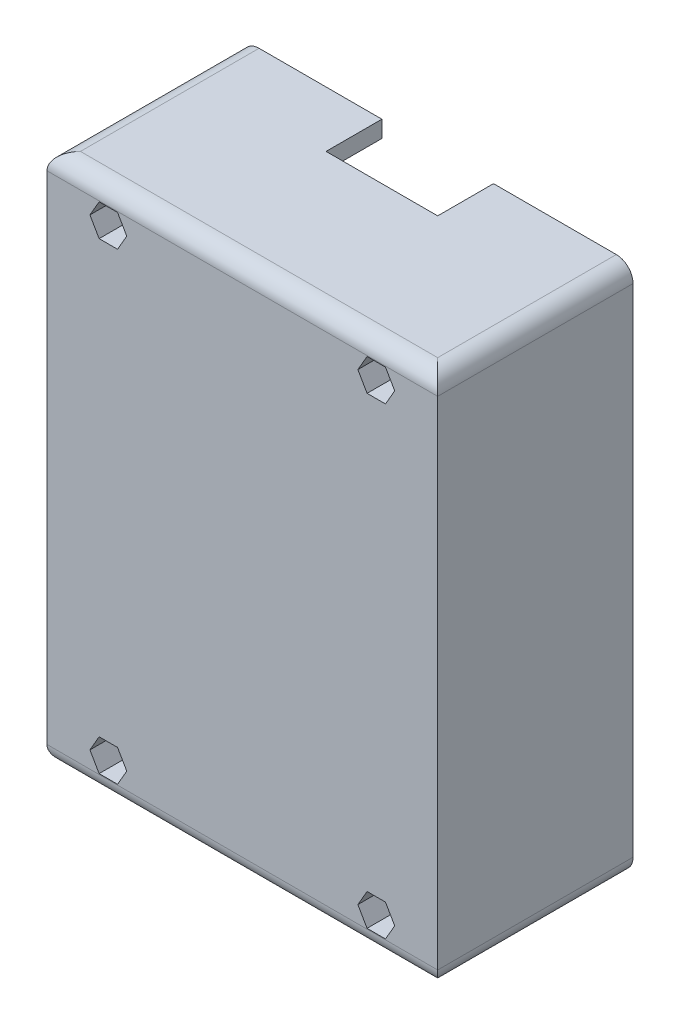
SolidWorks part; units mm, degrees
ref_plane "前视基准面" through (0, 0, 0) normal (0, 0, 1) x (1, 0, 0)
ref_plane "上视基准面" through (0, 0, 0) normal (0, 1, 0) x (1, 0, 0)
ref_plane "右视基准面" through (0, 0, 0) normal (1, 0, 0) x (0, 0, -1)
other "Configuration Table"
sketch "草图1" plane through (0, 0, 0) normal (1, 0, 0) x (0, 0, -1)
  line L1 (-17.5, -47.5) -> (17.5, -47.5)
  line L2 (-17.5, -47.5) -> (-17.5, 47.5)
  line L3 (-17.5, 47.5) -> (17.5, 47.5)
  line L4 (17.5, -47.5) -> (17.5, 47.5)
  line L5 (-17.5, -47.5) -> (17.5, 47.5) construction
  line L6 (-17.5, 47.5) -> (17.5, -47.5) construction
  point P0 (0, 0)
  dimension "D1" = 35
  dimension "D2" = 95
extrude "凸台-拉伸1" add sketch "草图1" along normal blind 60
sketch "草图4" plane through (0, 0, 17.5) normal (0, 0, 1) x (1, 0, 0)
  line L1 (50.7, 41.5) -> (52.35, 38.6421)
  line L2 (52.35, 38.6421) -> (55.65, 38.6421)
  line L3 (55.65, 38.6421) -> (57.3, 41.5)
  line L4 (57.3, 41.5) -> (55.65, 44.3579)
  line L5 (55.65, 44.3579) -> (52.35, 44.3579)
  line L6 (52.35, 44.3579) -> (50.7, 41.5)
  line L7 (9.3, 41.5) -> (7.65, 44.3579)
  line L8 (6, 41.5) -> (6, -41.5)
  line L9 (6, -41.5) -> (54, -41.5)
  line L10 (54, -41.5) -> (54, 41.5)
  line L11 (54, 41.5) -> (6, 41.5)
  line L12 (6, 41.5) -> (6, -41.5) construction
  line L13 (6, -41.5) -> (54, -41.5) construction
  line L14 (54, -41.5) -> (54, 41.5) construction
  line L15 (54, 41.5) -> (6, 41.5) construction
  line L16 (7.65, 44.3579) -> (4.35, 44.3579)
  line L17 (4.35, 44.3579) -> (2.7, 41.5)
  line L18 (2.7, 41.5) -> (4.35, 38.6421)
  line L19 (4.35, 38.6421) -> (7.65, 38.6421)
  line L20 (7.65, 38.6421) -> (9.3, 41.5)
  line L21 (9.3, -41.5) -> (7.65, -38.6421)
  line L22 (7.65, -38.6421) -> (4.35, -38.6421)
  line L23 (4.35, -38.6421) -> (2.7, -41.5)
  line L24 (2.7, -41.5) -> (4.35, -44.3579)
  line L25 (4.35, -44.3579) -> (7.65, -44.3579)
  line L26 (7.65, -44.3579) -> (9.3, -41.5)
  line L27 (50.7, -41.5) -> (52.35, -44.3579)
  line L28 (52.35, -44.3579) -> (55.65, -44.3579)
  line L29 (55.65, -44.3579) -> (57.3, -41.5)
  line L30 (57.3, -41.5) -> (55.65, -38.6421)
  line L31 (55.65, -38.6421) -> (52.35, -38.6421)
  line L32 (52.35, -38.6421) -> (50.7, -41.5)
  circle A0 centre (54, 41.5) radius 3.3 construction
  circle A1 centre (6, 41.5) radius 3.3 construction
  circle A2 centre (6, -41.5) radius 3.3 construction
  circle A3 centre (54, -41.5) radius 3.3 construction
  dimension "D2" = 6.6
  dimension "D3" = 6.6
  dimension "D4" = 6.6
  dimension "D5" = 6.6
  dimension "D1" = 6
extrude "切除-拉伸1" cut sketch "草图4" against normal blind 32
sketch "草图5" plane through (0, 0, 17.5) normal (0, 0, 1) x (1, 0, 0)
  circle A0 centre (54, 41.5) radius 1.6
  circle A1 centre (6, 41.5) radius 1.6
  circle A2 centre (54, -41.5) radius 1.6
  circle A3 centre (6, -41.5) radius 1.6
  dimension "D1" = 3.2
  dimension "D2" = 3.2
  dimension "D3" = 3.2
  dimension "D4" = 3.2
extrude "切除-拉伸2" cut sketch "草图5" against normal through all
sketch "草图6" plane through (0, 0, 0) normal (-1, 0, 0) x (0, 0, 1)
  line L4 (-17.5, 47.5) -> (-17.5, -47.5)
  line L5 (-17.5, -47.5) -> (17.5, -47.5)
  line L6 (17.5, -47.5) -> (17.5, 47.5)
  line L7 (17.5, 47.5) -> (-17.5, 47.5)
  line L8 (-17.5, 47.5) -> (-17.5, -47.5)
  line L9 (-17.5, -47.5) -> (17.5, -47.5)
  line L10 (17.5, -47.5) -> (17.5, 47.5)
  line L11 (17.5, 47.5) -> (-17.5, 47.5)
  dimension "D1" = 0
extrude "凸台-拉伸2" add sketch "草图6" along normal blind 5
sketch "草图7" plane through (60, 0, 0) normal (1, 0, 0) x (0, 0, -1)
  line L4 (17.5, -47.5) -> (17.5, 47.5)
  line L5 (17.5, 47.5) -> (-17.5, 47.5)
  line L6 (-17.5, 47.5) -> (-17.5, -47.5)
  line L7 (-17.5, -47.5) -> (17.5, -47.5)
  line L8 (17.5, -47.5) -> (17.5, 47.5)
  line L9 (17.5, 47.5) -> (-17.5, 47.5)
  line L10 (-17.5, 47.5) -> (-17.5, -47.5)
  line L11 (-17.5, -47.5) -> (17.5, -47.5)
  dimension "D1" = 0
extrude "凸台-拉伸3" add sketch "草图7" along normal blind 5
shell "抽壳1" thickness 3 removed face at (7.6, 41.5, -17.5)
ref_plane "基准面1" through (0, 0, -1.5) normal (0, 0, -1) x (-1, 0, 0)
sketch "草图8" plane through (0, 0, -1.5) normal (0, 0, -1) x (-1, 0, 0)
  line L0 (2, -44.5) -> (2, 44.5) construction
  line L5 (2, 29) -> (-6, 29)
  line L6 (-62, -44.5) -> (-62, 44.5) construction
  line L7 (-60, 34.5) -> (0, 34.5) construction
  line L8 (-60, 34.5) -> (-60, -15.5) construction
  line L9 (-60, -15.5) -> (0, -15.5) construction
  line L10 (0, 34.5) -> (0, -15.5) construction
  line L12 (-58, 32.5) -> (-58, -13.5) construction
  line L13 (-58, -13.5) -> (-2, -13.5) construction
  line L14 (-2, 32.5) -> (-2, -13.5) construction
  line L15 (-58, 32.5) -> (-2, 32.5) construction
  line L16 (-62, 36) -> (-54, 36)
  line L21 (2, 29) -> (2, 36)
  line L22 (2, 36) -> (-6, 36)
  line L23 (-6, 29) -> (-6, 36)
  line L24 (-2, 9.5) -> (-30, 9.5) construction
  line L25 (-30, 9.5) -> (-30, 18.3227) construction
  line L26 (-54, 29) -> (-54, 36)
  line L27 (-62, 29) -> (-54, 29)
  line L28 (-62, 29) -> (-62, 36)
  line L29 (2, -17) -> (-6, -17)
  line L30 (-6, -10) -> (-6, -17)
  line L31 (2, -10) -> (-6, -10)
  line L32 (2, -10) -> (2, -17)
  line L33 (-62, -10) -> (-62, -17)
  line L34 (-62, -10) -> (-54, -10)
  line L35 (-54, -10) -> (-54, -17)
  line L36 (-62, -17) -> (-54, -17)
  circle A0 centre (-2, 32.5) radius 1.5301
  circle A1 centre (-58, 32.5) radius 1.5301
  circle A2 centre (-2, -13.5) radius 1.5301
  circle A3 centre (-58, -13.5) radius 1.5301
  dimension "D1" = 60
  dimension "D2" = 50
  dimension "D3" = 2
  dimension "D6" = 7
  dimension "D7" = 3.5
  dimension "D8" = 8
  dimension "D5" = 2
extrude "凸台-拉伸4" add sketch "草图8" against normal blind 5
sketch "草图9" plane through (54, 0, 0) normal (-1, 0, 0) x (0, 0, 1)
  line L0 (0.3, 35.25) -> (0.3, 29.75)
  line L4 (2.8, 35.25) -> (2.8, 29.75)
  line L5 (-1.5, 36) -> (-1.5, 29) construction
  line L7 (3.5, 29) -> (3.5, -10) construction
  line L8 (0.3, 29.75) -> (2.8, 29.75)
  line L9 (0.3, 35.25) -> (2.8, 35.25)
  line L10 (3.5, 9.5) -> (5.2406, 9.5) construction
  line L15 (0.3, -16.25) -> (2.8, -16.25)
  line L16 (0.3, -10.75) -> (2.8, -10.75)
  line L17 (2.8, -16.25) -> (2.8, -10.75)
  line L18 (0.3, -16.25) -> (0.3, -10.75)
  dimension "D1" = 1.8
  dimension "D2" = 2.5
  dimension "D3" = 5.5
extrude "切除-拉伸3" cut sketch "草图9" against normal blind 7.5
sketch "草图10" plane through (6, 0, 0) normal (1, 0, 0) x (0, 0, -1)
  line L0 (6.3943, 32.5) -> (-4.2908, 32.5) construction
  line L1 (-2.8, 35.25) -> (-0.3, 35.25)
  line L2 (-2.8, 35.25) -> (-2.8, 29.75)
  line L3 (-2.8, 29.75) -> (-0.3, 29.75)
  line L4 (-0.3, 35.25) -> (-0.3, 29.75)
  line L5 (-3.5, 29) -> (1.5, 29) construction
  line L6 (1.5, 35.6421) -> (1.5, 29) construction
  line L7 (1.5, 29) -> (1.5, -10) construction
  line L8 (1.5, 9.5) -> (0, 9.5) construction
  line L9 (-0.3, -16.25) -> (-0.3, -10.75)
  line L10 (-2.8, -10.75) -> (-0.3, -10.75)
  line L11 (-2.8, -16.25) -> (-2.8, -10.75)
  line L12 (-2.8, -16.25) -> (-0.3, -16.25)
  line L13 (6.3943, -13.5) -> (-4.2908, -13.5) construction
  dimension "D1" = 3.5
  dimension "D2" = 1.8
  dimension "D3" = 2.5
  dimension "D4" = 2.75
  dimension "D5" = 2.75
extrude "切除-拉伸4" cut sketch "草图10" against normal up to surface (8 mm away) up to face at (-2, -13.5, 1)
sketch "草图11" plane through (0, 0, 14.5) normal (0, 0, -1) x (-1, 0, 0)
  line L0 (-62, -44.5) -> (-62, 44.5) construction
  line L1 (-39, 34.5) -> (-34, 34.5)
  line L2 (-39, 34.5) -> (-39, 29.5)
  line L3 (-39, 29.5) -> (-34, 29.5)
  line L4 (-34, 34.5) -> (-34, 29.5)
  line L5 (-26, 34.5) -> (-21, 34.5)
  line L6 (-26, 34.5) -> (-26, 29.5)
  line L7 (-26, 29.5) -> (-21, 29.5)
  line L8 (-21, 34.5) -> (-21, 29.5)
  line L9 (-39, 4.5) -> (-34, 4.5)
  line L10 (-39, 4.5) -> (-39, -0.5)
  line L11 (-39, -0.5) -> (-34, -0.5)
  line L12 (-34, 4.5) -> (-34, -0.5)
  line L13 (-26, 4.5) -> (-21, 4.5)
  line L14 (-26, 4.5) -> (-26, -0.5)
  line L15 (-26, -0.5) -> (-21, -0.5)
  line L16 (-21, 4.5) -> (-21, -0.5)
  dimension "D1" = 5
  dimension "D2" = 5
  dimension "D3" = 5
  dimension "D4" = 5
  dimension "D5" = 5
  dimension "D6" = 5
  dimension "D7" = 5
  dimension "D8" = 5
  dimension "D9" = 8
  dimension "D10" = 8
  dimension "D11" = 23
  dimension "D12" = 23
  dimension "D13" = 35
extrude "凸台-拉伸5" add sketch "草图11" along normal blind 16
ref_plane "基准面3" through (0, 17, 0) normal (0, 1, 0) x (1, 0, 0)
sketch "草图12" plane through (0, 29.5, 0) normal (0, -1, 0) x (1, 0, 0)
  line L0 (30, 14.5) -> (30, 7.5) construction
  line L1 (48.9679, 14.5) -> (11.0321, 14.5) construction
  circle A0 centre (30, 7.5) radius 7
  dimension "D1" = 7
extrude "切除-拉伸5" cut sketch "草图12" along normal blind 40 and the other way blind 10
sketch "草图13" plane through (0, 29.5, 0) normal (0, -1, 0) x (1, 0, 0)
  line L0 (39, 4) -> (46, 14.5)
  line L1 (39, -1.5) -> (39, 14.5) construction
  line L2 (48.9679, 14.5) -> (11.0321, 14.5) construction
  line L3 (46, 14.5) -> (39, 14.5)
  line L4 (39, 14.5) -> (39, 4)
  line L5 (21, 6.5) -> (14, 14.5)
  line L6 (21, -1.5) -> (21, 14.5) construction
  line L7 (14, 14.5) -> (21, 14.5)
  line L8 (21, 14.5) -> (21, 6.5)
  dimension "D1" = 7
  dimension "D2" = 7
extrude "凸台-拉伸6" add sketch "草图13" against normal up to surface (5 mm away) up to face at (23.8333, 34.5, 6.8333)
sketch "草图15" plane through (0, -0.5, 0) normal (0, -1, 0) x (1, 0, 0)
  line L0 (39, 6.5) -> (46, 14.5)
  line L1 (39, -1.5) -> (39, 14.5) construction
  line L2 (48.9679, 14.5) -> (11.0321, 14.5) construction
  line L3 (46, 14.5) -> (34, 14.5) construction
  line L4 (46, 14.5) -> (39, 14.5)
  line L5 (39, 14.5) -> (39, 6.5)
  line L6 (21, 6.5) -> (21, 14.5)
  line L7 (21, -1.5) -> (21, 14.5) construction
  line L8 (26, 14.5) -> (14, 14.5) construction
  line L9 (21, 14.5) -> (14, 14.5)
  line L10 (14, 14.5) -> (21, 6.5)
extrude "凸台-拉伸7" add sketch "草图15" against normal up to surface (5 mm away) up to face at (23.8333, 4.5, 6.8333)
sketch "草图16" plane through (0, -44.5, 0) normal (0, 1, 0) x (1, 0, 0)
  line L0 (10.0866, 1.5) -> (51.5542, 1.5) construction
  line L2 (8.25, 5) -> (15.25, 5)
  line L3 (8.25, 5) -> (8.25, -2)
  line L4 (30, 1.5) -> (30, 12.3494) construction
  line L5 (48.25, 7.1155) -> (48.25, -4.8995) construction
  line L6 (11.75, 7.6617) -> (11.75, -3.3066) construction
  line L7 (8.25, -2) -> (15.25, -2)
  line L8 (15.25, 5) -> (15.25, -2)
  line L9 (8.25, 5) -> (15.25, -2) construction
  line L10 (8.25, -2) -> (15.25, 5) construction
  line L11 (44.75, 5) -> (51.75, 5)
  line L12 (44.75, 5) -> (44.75, -2)
  line L13 (44.75, -2) -> (51.75, -2)
  line L14 (51.75, 5) -> (51.75, -2)
  line L15 (44.75, 5) -> (51.75, -2) construction
  line L16 (44.75, -2) -> (51.75, 5) construction
  point P2 (11.75, 1.5)
  point P13 (48.25, 1.5)
  dimension "D1" = 18.25
  dimension "D2" = 18.25
  dimension "D3" = 7
  dimension "D4" = 7
  dimension "D5" = 7
  dimension "D6" = 7
extrude "凸台-拉伸8" add sketch "草图16" along normal up to surface (8.8579 mm away) up to face at (6, -35.6421, -1.5)
sketch "草图19" plane through (0, 0, 17.5) normal (0, 0, 1) x (1, 0, 0)
  line L0 (7.65, -44.3579) -> (9.3, -41.5) construction
  line L1 (9.3, -41.5) -> (7.65, -38.6421) construction
  line L2 (7.65, -38.6421) -> (4.35, -38.6421) construction
  line L3 (4.35, -38.6421) -> (2.7, -41.5) construction
  line L4 (2.7, -41.5) -> (4.35, -44.3579) construction
  line L5 (4.35, -44.3579) -> (7.65, -44.3579) construction
  line L7 (8.25, -43.3187) -> (9.3, -41.5) construction
  line L8 (9.3, -41.5) -> (8.25, -39.6813) construction
  line L9 (7.65, -44.3579) -> (9.3, -41.5)
  line L10 (9.3, -41.5) -> (7.65, -38.6421)
  line L11 (7.65, -38.6421) -> (4.35, -38.6421)
  line L12 (4.35, -38.6421) -> (2.7, -41.5)
  line L13 (2.7, -41.5) -> (4.35, -44.3579)
  line L14 (4.35, -44.3579) -> (7.65, -44.3579)
  line L16 (8.25, -43.3187) -> (9.3, -41.5)
  line L17 (9.3, -41.5) -> (8.25, -39.6813)
  line L19 (51.75, -39.6813) -> (50.7, -41.5) construction
  line L20 (50.7, -41.5) -> (51.75, -43.3187) construction
  line L21 (52.35, -38.6421) -> (50.7, -41.5) construction
  line L22 (50.7, -41.5) -> (52.35, -44.3579) construction
  line L23 (52.35, -44.3579) -> (55.65, -44.3579) construction
  line L24 (55.65, -44.3579) -> (57.3, -41.5) construction
  line L25 (57.3, -41.5) -> (55.65, -38.6421) construction
  line L26 (55.65, -38.6421) -> (52.35, -38.6421) construction
  line L28 (51.75, -39.6813) -> (50.7, -41.5)
  line L29 (50.7, -41.5) -> (51.75, -43.3187)
  line L30 (52.35, -38.6421) -> (50.7, -41.5)
  line L31 (50.7, -41.5) -> (52.35, -44.3579)
  line L32 (52.35, -44.3579) -> (55.65, -44.3579)
  line L33 (55.65, -44.3579) -> (57.3, -41.5)
  line L34 (57.3, -41.5) -> (55.65, -38.6421)
  line L35 (55.65, -38.6421) -> (52.35, -38.6421)
  line M7 (52.35, -44.3579) -> (50.7, -41.5)
  line M8 (50.7, -41.5) -> (52.35, -38.6421)
  line M9 (52.35, -38.6421) -> (55.65, -38.6421)
  line M10 (55.65, -38.6421) -> (57.3, -41.5)
  line M11 (57.3, -41.5) -> (55.65, -44.3579)
  line M12 (55.65, -44.3579) -> (52.35, -44.3579)
  line M13 (7.65, -38.6421) -> (9.3, -41.5)
  line M14 (9.3, -41.5) -> (7.65, -44.3579)
  line M15 (7.65, -44.3579) -> (4.35, -44.3579)
  line M16 (4.35, -44.3579) -> (2.7, -41.5)
  line M17 (2.7, -41.5) -> (4.35, -38.6421)
  line M18 (4.35, -38.6421) -> (7.65, -38.6421)
extrude "切除-拉伸6" cut sketch "草图19" against normal up to next contours L9 L10 M13 M18 M17 M16 M15 M14 | M7 M12 M11 M10 M9 M8 region at (6, -41.5, 17.5) region at (54, -41.5, 17.5)
sketch "草图20" plane through (15.25, 0, 0) normal (1, 0, 0) x (0, 0, -1)
  line L0 (-2, -37.2421) -> (5, -37.2421) construction
  line L1 (-2, -35.6421) -> (-2, -44.5) construction
  line L2 (5, -35.6421) -> (5, -44.5) construction
  line L3 (4.25, -37.2421) -> (4.25, -40.1454)
  line L4 (-2, -35.6421) -> (5, -35.6421) construction
  line L5 (1.5, -37.2421) -> (1.5, -41.7415) construction
  line L6 (-1.25, -37.2421) -> (-1.25, -40.1454)
  line L7 (-1.25, -40.1454) -> (4.25, -40.1454)
  line L8 (-1.25, -37.2421) -> (4.25, -37.2421)
  dimension "D1" = 2.75
  dimension "D2" = 2.75
  dimension "D3" = 1.6
extrude "切除-拉伸7" cut sketch "草图20" against normal blind 7
ref_plane "基准面4" through (30, 0, 0) normal (1, 0, 0) x (0, 0, -1)
mirror "镜向3" about plane through (30, 0, 0) normal (1, 0, 0) of "切除-拉伸7"
sketch "草图21" plane through (0, -35.6421, 0) normal (0, 1, 0) x (1, 0, 0)
  line L0 (8.4269, 1.5) -> (53.6986, 1.5) construction
  line L1 (15.25, 5) -> (44.75, 5) construction
  line L2 (30, 5) -> (30, 12.0164) construction
  circle A0 centre (48.25, 1.5) radius 1.6
  circle A1 centre (11.75, 1.5) radius 1.6
  dimension "D1" = 3.2
  dimension "D2" = 3.2
  dimension "D3" = 18.25
  dimension "D4" = 18.25
extrude "切除-拉伸8" cut sketch "草图21" against normal through all
sketch "草图22" plane through (0, -47.5, 0) normal (0, -1, 0) x (1, 0, 0)
  line L0 (65, -17.5) -> (-5, -17.5) construction
  line L1 (19.75, 8.5) -> (23.75, 8.5)
  line L2 (19.75, 8.5) -> (19.75, -9.5)
  line L3 (19.75, -9.5) -> (23.75, -9.5)
  line L4 (23.75, 8.5) -> (23.75, -9.5)
  line L5 (28, 8.5) -> (32, 8.5)
  line L6 (28, 8.5) -> (28, -9.5)
  line L7 (28, -9.5) -> (32, -9.5)
  line L8 (32, 8.5) -> (32, -9.5)
  line L9 (36.25, 8.5) -> (40.25, 8.5)
  line L10 (36.25, 8.5) -> (36.25, -9.5)
  line L11 (36.25, -9.5) -> (40.25, -9.5)
  line L12 (40.25, 8.5) -> (40.25, -9.5)
  circle A0 centre (11.75, -1.5) radius 1.6 construction
  circle A1 centre (48.25, -1.5) radius 1.6 construction
  dimension "D7" = 8
  dimension "D8" = 8
  dimension "D1" = 4
  dimension "D2" = 4
  dimension "D3" = 4
  dimension "D4" = 18
  dimension "D5" = 18
  dimension "D6" = 18
  dimension "D9" = 8
  dimension "D10" = 8
  dimension "D11" = 8
  dimension "D12" = 4.25
extrude "切除-拉伸9" cut sketch "草图22" against normal blind 7
sketch "草图23" plane through (0, 47.5, 0) normal (0, 1, 0) x (1, 0, 0)
  line L0 (65, 17.5) -> (-5, 17.5) construction
  line L1 (20, 17.5) -> (40, 17.5)
  line L2 (20, 17.5) -> (20, 7.5)
  line L3 (20, 7.5) -> (40, 7.5)
  line L4 (40, 17.5) -> (40, 7.5)
  line L5 (65, 17.5) -> (65, -17.5) construction
  line L6 (-5, -17.5) -> (-5, 17.5) construction
  dimension "D1" = 25
  dimension "D2" = 25
  dimension "D3" = 10
extrude "切除-拉伸10" cut sketch "草图23" against normal blind 10
fillet "圆角3" radius 3 6 edges at (65, -47.5, 0) (30, -47.5, 17.5) (-5, -47.5, 0) (65, 47.5, 0) (30, 47.5, 17.5) (-5, 47.5, 0)
